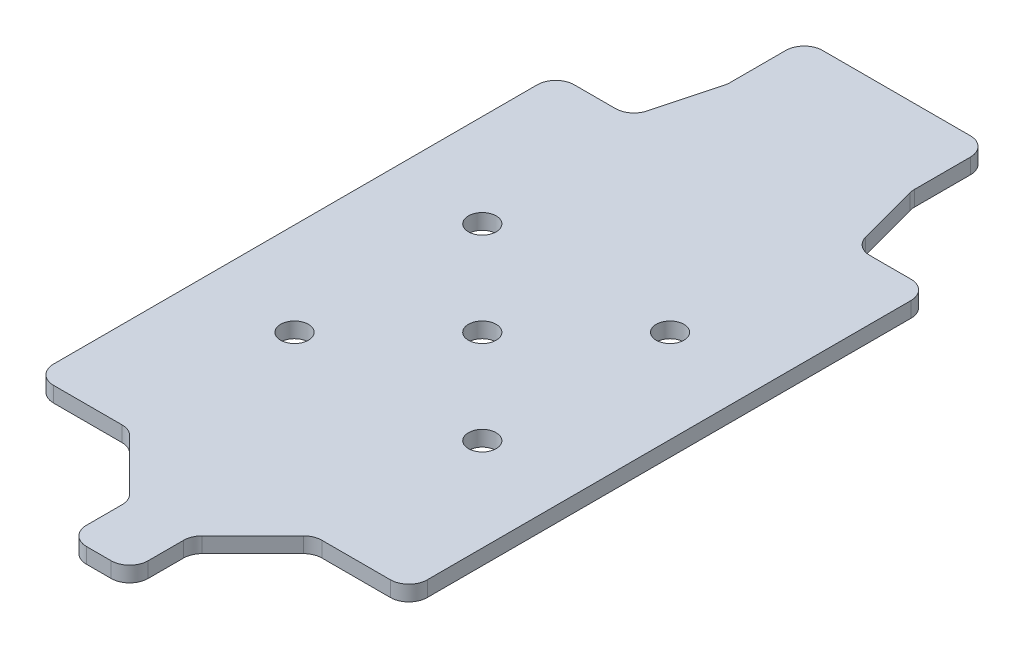
SolidWorks part; units mm, degrees
material "Thornel Mat VMA"
ref_plane "Front Plane" through (0, 0, 0) normal (0, 0, 1) x (1, 0, 0)
ref_plane "Top Plane" through (0, 0, 0) normal (0, 1, 0) x (1, 0, 0)
ref_plane "Right Plane" through (0, 0, 0) normal (1, 0, 0) x (0, 0, -1)
sketch "Sketch1" plane through (0, 0, 0) normal (0, 1, 0) x (1, 0, 0)
  line L0 (0, 42.2818) -> (0, 67.2818) construction
  line L1 (-30.35, 42.2818) -> (30.35, 42.2818)
  line L2 (-30.35, 42.2818) -> (-30.35, -42.2818)
  line L3 (-30.35, -42.2818) -> (30.35, -42.2818)
  line L4 (30.35, 42.2818) -> (30.35, -42.2818)
  line L5 (-30.35, 42.2818) -> (30.35, -42.2818) construction
  line L6 (-30.35, -42.2818) -> (30.35, 42.2818) construction
  line L7 (-15.25, -15.25) -> (15.25, -15.25) construction
  line L8 (-15.25, -15.25) -> (-15.25, 15.25) construction
  line L9 (-15.25, 15.25) -> (15.25, 15.25) construction
  line L10 (15.25, -15.25) -> (15.25, 15.25) construction
  line L11 (-15.25, -15.25) -> (15.25, 15.25) construction
  line L12 (-15.25, 15.25) -> (15.25, -15.25) construction
  line L13 (-15, 67.2818) -> (15, 67.2818)
  line L14 (-18.3494, 42.2818) -> (-15, 54.7818)
  line L15 (-15, 54.7818) -> (-15, 67.2818)
  line L16 (15, 54.7818) -> (15, 67.2818)
  line L17 (18.3494, 42.2818) -> (15, 54.7818)
  line L18 (0, -42.2818) -> (0, -62.2818) construction
  line L19 (-5, -62.2818) -> (5, -62.2818)
  line L20 (-5, -62.2818) -> (-5, -52.2818)
  line L21 (-5, -52.2818) -> (-15, -42.2818)
  line L22 (5, -52.2818) -> (15, -42.2818)
  line L23 (5, -62.2818) -> (5, -52.2818)
  point P0 (0, 0)
  point P6 (0, 0)
  point P16 (0, 67.2818)
  point P22 (-7.5, -55.2012)
  point P25 (0, -62.2818)
  point P28 (-7.5, -51.8869)
  dimension "D1" = 60.7
  dimension "D2" = 30.5
  dimension "D3" = 84.5637
  dimension "D4" = 30
  dimension "D5" = 75
  dimension "D6" = 25
  dimension "D7" = 12.5
  dimension "D8" = 10
  dimension "D9" = 20
  dimension "D10" = 45
  dimension "D11" = 10
extrude "Boss-Extrude1" add sketch "Sketch1" along normal mid plane 2.5 contours L13 L15 L1 | L4 L1 L2 L3 | L19 L23 L22 L3 L21 L20 region at (0, 0, 0) region at (0, 0, -54.3412) region at (0, 0, 50.0596)
hole_wizard "M4 Clearance Hole1" positions "Sketch2" profile "Sketch3" hole size "M4" standard "ANSI Metric"
sketch "Sketch2" plane through (0, 1.25, 0) normal (0, 1, 0) x (1, 0, 0)
  line L1 (-15.25, -15.25) -> (15.25, -15.25) construction
  line L2 (-15.25, -15.25) -> (-15.25, 15.25) construction
  line L3 (-15.25, 15.25) -> (15.25, 15.25) construction
  line L4 (15.25, -15.25) -> (15.25, 15.25) construction
  line L5 (-15.25, -15.25) -> (15.25, 15.25) construction
  line L6 (-15.25, 15.25) -> (15.25, -15.25) construction
  point P1 (0, 0)
  point P2 (15.25, 15.25)
  point P73 (-15.25, -15.25)
  point P74 (-15.25, 15.25)
  point P75 (15.25, -15.25)
  dimension "D1" = 30.5
sketch "Sketch3" plane through (0, 1.25, 0) normal (1, 0, 0) x (0, 0, 1)
  line L0 (0, 0) -> (0, 6.5519)
  line L1 (0, 6.5519) -> (2.25, 5.2)
  line L2 (2.25, 5.2) -> (2.25, 0)
  line L5 (2.25, 0) -> (0, 0)
  line L10 (0, 6.5519) -> (-2.25, 5.2) construction
  line L11 (0, -6.35) -> (0, 107.95) construction
  dimension "Hole Dia." = 4.5
  dimension "Hole Depth" = 5.2
  dimension "Drill Angle" = 118
fillet "Fillet1" radius 3 16 edges at (30.35, 0, -42.2818) (30.35, 0, 42.2818) (-30.35, 0, 42.2818) (-30.35, 0, -42.2818) (-15, 0, -67.2818) (18.3494, 0, -42.2818) (15, 0, -54.7818) (15, 0, -67.2818) (-15, 0, -54.7818) (-18.3494, 0, -42.2818) (15, 0, 42.2818) (5, 0, 52.2818) (5, 0, 62.2818) (-5, 0, 62.2818) (-5, 0, 52.2818) (-15, 0, 42.2818)
